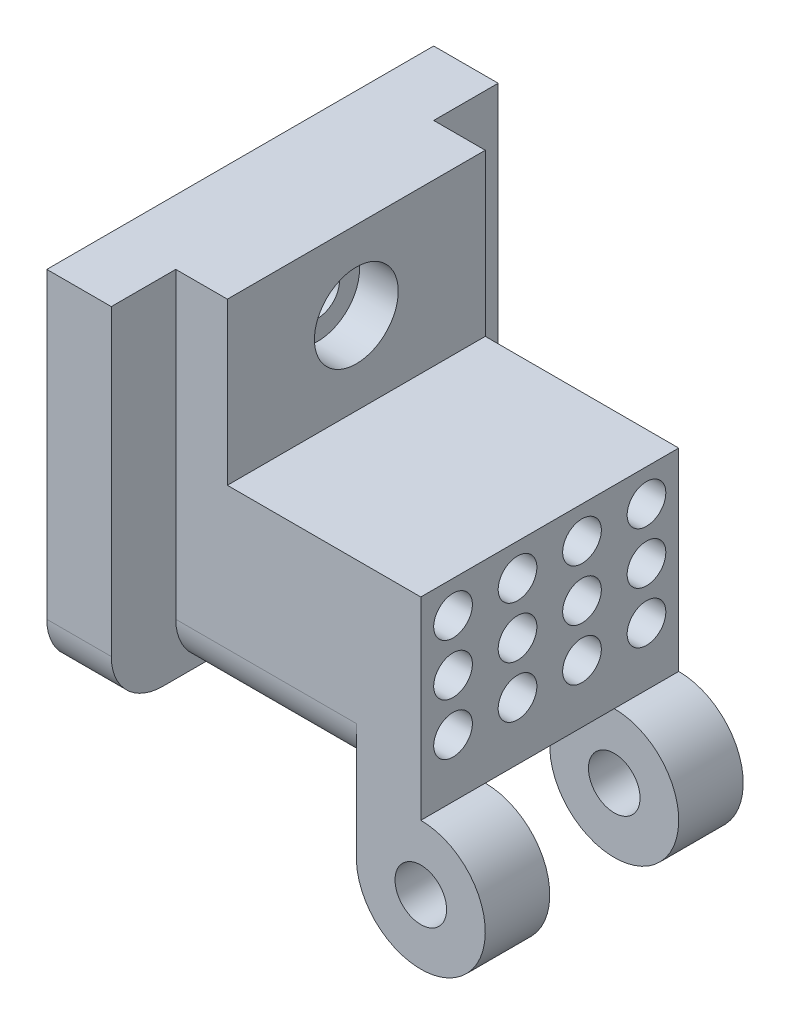
SolidWorks part; units mm, degrees
ref_plane "Front Plane" through (0, 0, 0) normal (0, 0, 1) x (1, 0, 0)
ref_plane "Top Plane" through (0, 0, 0) normal (0, 1, 0) x (1, 0, 0)
ref_plane "Right Plane" through (0, 0, 0) normal (1, 0, 0) x (0, 0, -1)
sketch "Sketch1" plane through (0, 0, 0) normal (1, 0, 0) x (0, 0, -1)
  line L1 (-10, -7.5) -> (10, -7.5)
  line L2 (-10, -7.5) -> (-10, 7.5)
  line L3 (-10, 7.5) -> (10, 7.5)
  line L4 (10, -7.5) -> (10, 7.5)
  line L5 (-10, -7.5) -> (10, 7.5) construction
  line L6 (-10, 7.5) -> (10, -7.5) construction
  point P0 (0, 0)
  dimension "D1" = 20
  dimension "D2" = 15
extrude "Boss-Extrude1" add sketch "Sketch1" along normal blind 15
sketch "Sketch2" plane through (0, 0, 10) normal (0, 0, 1) x (1, 0, 0)
  line L0 (15, -7.5) -> (10.0156, -7.5)
  line L1 (10.0156, -12.1058) -> (10.0156, -7.5)
  line L2 (15, -7.5) -> (0, -7.5) construction
  circle A0 centre (15, -12.5) radius 2
  arc A2 (10.0156, -12.1058) -> (15, -7.5) centre (15, -12.5) ccw
  arc A3 (10.0156, -12.1058) -> (15, -7.5) centre (15, -12.5) cw construction
  dimension "D1" = 4
extrude "Boss-Extrude2" add sketch "Sketch2" against normal blind 5
mirror "Mirror1" about plane through (0, 0, 0) normal (0, 0, 1) of "Boss-Extrude2"
sketch "Sketch3" plane through (0, 7.5, 0) normal (0, -1, 0) x (1, 0, 0)
  line L4 (-4, 10) -> (-4, 15)
  line L5 (-4, 15) -> (-9, 15)
  line L6 (-9, 15) -> (-9, -15)
  line L7 (-9, -15) -> (-4, -15)
  line L8 (-4, -15) -> (-4, -10)
  line L9 (-4, 10) -> (0, 10)
  line L10 (0, 10) -> (0, -10)
  line L11 (0, -10) -> (-4, -10)
  point P3 (-9, 0)
  dimension "D1" = 30
  dimension "D2" = 5
  dimension "D3" = 4
extrude "Boss-Extrude3" add sketch "Sketch3" along normal up to surface (15 mm away) and the other way blind 12.5 up to face at (8.7578, -7.5, 0)
fillet "Fillet1" radius 4 4 edges at (-6.5, -7.5, -15) (3.0078, -7.5, -10) (3.0078, -7.5, 10) (-6.5, -7.5, 15)
hole_wizard "M3x0.5 Tapped Hole1" positions "Sketch4" profile "Sketch5" tap size "M3x0.5" standard "ANSI Metric"
sketch "Sketch4" plane through (0, 0, 0) normal (1, 0, 0) x (0, 0, -1)
  point P0 (0, 13.9088)
sketch "Sketch5" plane through (0, 13.9088, 0) normal (0, 1, 0) x (0, 0, -1)
  line L0 (0, 0) -> (0, 11.7511)
  line L1 (0, 11.7511) -> (1.25, 11)
  line L2 (1.25, 11) -> (1.25, 0)
  line L3 (1.25, 0) -> (0, 0)
  line L4 (0, 11.7511) -> (-1.25, 11) construction
  line L5 (0, -6.35) -> (0, 107.95) construction
  dimension "Tap Drill Dia." = 2.5
  dimension "Tap Drill Depth" = 11
  dimension "Drill Angle" = 118
cosmetic thread "Hole Thread1" parameters "D1"=6.1, "D2"=3
hole_wizard "CBORE for M3 SHCS1" positions "Sketch6" profile "Sketch7" counterbore size "M3" standard "ANSI Metric"
sketch "Sketch6" plane through (0, 0, 0) normal (1, 0, 0) x (0, 0, -1)
  point P0 (0, 13.9088)
sketch "Sketch7" plane through (0, 13.9088, 0) normal (0, 1, 0) x (0, 0, -1)
  line L0 (0, 0) -> (0, 10.0215)
  line L1 (0, 10.0215) -> (1.7, 9)
  line L2 (1.7, 9) -> (1.7, 3)
  line L3 (1.7, 3) -> (3.25, 3)
  line L4 (3.25, 3) -> (3.25, 0)
  line L5 (3.25, 0) -> (0, 0)
  line L6 (0, 10.0215) -> (-1.7, 9) construction
  line L7 (0, -6.35) -> (0, 107.95) construction
  dimension "Hole Dia." = 3.4
  dimension "Hole Depth" = 9
  dimension "C'Bore Dia." = 6.5
  dimension "C'Bore Depth" = 3
  dimension "Drill Angle" = 118
sketch "Sketch8" plane through (15, 0, 0) normal (1, 0, 0) x (0, 0, -1)
  line L0 (-10, 7.5) -> (-10, -7.5) construction
  line L1 (10, 7.5) -> (-10, 7.5) construction
  line L2 (10, -7.5) -> (10, 7.5) construction
  line L3 (-10, -7.5) -> (-5, -7.5) construction
  circle A0 centre (-7.5, 5) radius 1.5
  circle A1 centre (-2.5, 5) radius 1.5
  circle A2 centre (2.5, 5) radius 1.5
  circle A3 centre (7.5, 5) radius 1.5
  circle A4 centre (-2.5, 1) radius 1.5
  circle A5 centre (2.5, 1) radius 1.5
  circle A6 centre (7.5, 1) radius 1.5
  circle A7 centre (-2.5, -3) radius 1.5
  circle A8 centre (2.5, -3) radius 1.5
  circle A9 centre (7.5, -3) radius 1.5
  circle A10 centre (-7.5, 1) radius 1.5
  circle A11 centre (-7.5, -3) radius 1.5
  point P2 (-7.234, 5.1661)
  point P3 (2.3784, 5.1424)
  point P30 (-7.5535, 4.8591)
  point P31 (6.1011, 5)
  point P32 (6.391, 5)
  point P35 (0, 0)
  point P36 (0, 0)
  dimension "D1" = 3
  dimension "D4" = 2.5
  dimension "D5" = 2.5
  dimension "D6" = 2.5
  dimension "D7" = 4.5
  dimension "D2" = 4
  dimension "D3" = 3
extrude "Cut-Extrude1" cut sketch "Sketch8" against normal blind 2.5
